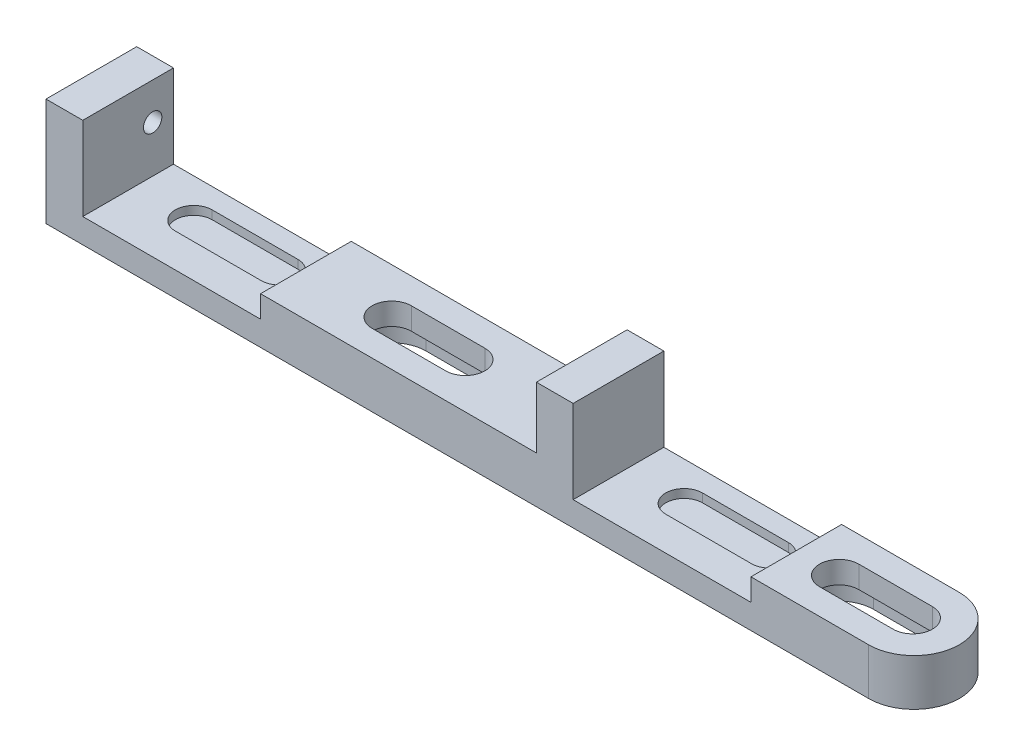
SolidWorks part; units mm, degrees
material "6061 Alloy"
ref_plane "Front Plane" through (0, 0, 0) normal (0, 0, 1) x (1, 0, 0)
ref_plane "Top Plane" through (0, 0, 0) normal (0, 1, 0) x (1, 0, 0)
ref_plane "Right Plane" through (0, 0, 0) normal (1, 0, 0) x (0, 0, -1)
sketch "Sketch1" plane through (0, 0, 0) normal (0, 0, 1) x (1, 0, 0)
  line L0 (0, 0) -> (0, 8.8)
  line L1 (0, 0) -> (70.8, 0)
  line L8 (70.8, 0) -> (70.8, 3.8)
  line L10 (0, 8.8) -> (3, 8.8)
  line L11 (3, 8.8) -> (3, 2)
  line L20 (40, 3.8) -> (40, 8.8)
  line L21 (40, 8.8) -> (43, 8.8)
  line L22 (43, 8.8) -> (43, 2)
  line L23 (40, 3.8) -> (17.5, 3.8)
  line L24 (17.5, 3.8) -> (17.5, 2)
  line L25 (17.5, 2) -> (3, 2)
  line L26 (70.8, 3.8) -> (57.5, 3.8)
  line L27 (57.5, 3.8) -> (57.5, 2)
  line L28 (57.5, 2) -> (43, 2)
  dimension "D1" = 3
  dimension "D2" = 2
  dimension "D3" = 8.8
  dimension "D4" = 3.8
  dimension "D5" = 14.5
  dimension "D6" = 3
  dimension "D7" = 40
  dimension "D8" = 14.5
  dimension "D10" = 70.8
extrude "Boss-Extrude1" add sketch "Sketch1" along normal blind 7.4
sketch "Sketch3" plane through (0, 3.8, 0) normal (0, 1, 0) x (1, 0, 0)
  line L0 (30.5, -3.7) -> (24.5, -3.7) construction
  line L1 (30.5, -5.3) -> (24.5, -5.3)
  line L2 (30.5, -2.1) -> (24.5, -2.1)
  line L3 (67, -3.7) -> (61, -3.7) construction
  line L4 (67, -5.3) -> (61, -5.3)
  line L5 (67, -2.1) -> (61, -2.1)
  line L6 (40, -7.4) -> (40, 0) construction
  arc A0 (30.5, -5.3) -> (30.5, -2.1) centre (30.5, -3.7) ccw
  arc A1 (24.5, -2.1) -> (24.5, -5.3) centre (24.5, -3.7) ccw
  arc A2 (67, -5.3) -> (67, -2.1) centre (67, -3.7) ccw
  arc A3 (61, -2.1) -> (61, -5.3) centre (61, -3.7) ccw
  point P2 (27.5, -3.7)
  point P7 (64, -3.7)
  point P21 (40, -3.7)
  dimension "D2" = 1.6
  dimension "D1" = 6
  dimension "D3" = 12.5
  dimension "D4" = 36.5
extrude "Cut-Extrude1" cut sketch "Sketch3" against normal blind 10
sketch "Sketch4" plane through (0, 0, 0) normal (0, -1, 0) x (1, 0, 0)
  line L0 (24.5, 5.3) -> (30.5, 5.3) construction
  line L1 (30.5, 2.1) -> (24.5, 2.1) construction
  line L2 (24.5, 5.3) -> (30.5, 5.3)
  line L3 (30.5, 2.1) -> (24.5, 2.1)
  line L4 (61, 5.3) -> (67, 5.3) construction
  line L5 (67, 2.1) -> (61, 2.1) construction
  line L6 (61, 5.3) -> (67, 5.3)
  line L7 (67, 2.1) -> (61, 2.1)
  line L8 (24.5, 6.5) -> (30.5, 6.5)
  line L9 (30.5, 0.9) -> (24.5, 0.9)
  line L10 (61, 6.5) -> (67, 6.5)
  line L11 (67, 0.9) -> (61, 0.9)
  arc A0 (30.5, 2.1) -> (30.5, 5.3) centre (30.5, 3.7) ccw construction
  arc A1 (24.5, 5.3) -> (24.5, 2.1) centre (24.5, 3.7) ccw construction
  arc A2 (30.5, 2.1) -> (30.5, 5.3) centre (30.5, 3.7) ccw
  arc A3 (24.5, 5.3) -> (24.5, 2.1) centre (24.5, 3.7) ccw
  arc A4 (61, 5.3) -> (61, 2.1) centre (61, 3.7) ccw construction
  arc A5 (67, 2.1) -> (67, 5.3) centre (67, 3.7) ccw construction
  arc A6 (61, 5.3) -> (61, 2.1) centre (61, 3.7) ccw
  arc A7 (67, 2.1) -> (67, 5.3) centre (67, 3.7) ccw
  arc A8 (30.5, 0.9) -> (30.5, 6.5) centre (30.5, 3.7) ccw
  arc A9 (24.5, 6.5) -> (24.5, 0.9) centre (24.5, 3.7) ccw
  arc A10 (67, 0.9) -> (67, 6.5) centre (67, 3.7) ccw
  arc A11 (61, 6.5) -> (61, 0.9) centre (61, 3.7) ccw
  dimension "D1" = 1.2
  dimension "D2" = 1.2
extrude "Cut-Extrude2" cut sketch "Sketch4" against normal blind 2
sketch "Sketch5" plane through (0, 0, 0) normal (-1, 0, 0) x (0, 0, 1)
  line L0 (7.4, 8.8) -> (0, 8.8) construction
  line L2 (7.4, 8.8) -> (7.4, 0) construction
  circle A0 centre (1.7, 5.8) radius 0.75
  dimension "D1" = 1.5
  dimension "D2" = 3
  dimension "D3" = 5.7
extrude "Cut-Extrude3" cut sketch "Sketch5" against normal up to next
sketch "Sketch6" plane through (0, 0, 0) normal (0, -1, 0) x (1, 0, 0)
  line L0 (70.8, 0) -> (70.8, 7.4)
  line L1 (70.8, 7.4) -> (70.8, 0) construction
  line L2 (70.8, 7.4) -> (67.1, 7.4)
  line L3 (0, 7.4) -> (70.8, 7.4) construction
  line L4 (0, 0) -> (70.8, 0) construction
  line L5 (67.1, 0) -> (70.8, 0)
  arc A0 (67.1, 7.4) -> (67.1, 0) centre (67.1, 3.7) cw
extrude "Cut-Extrude4" cut sketch "Sketch6" against normal blind 10 contours A0 | A0 L0 region at (69.9735, 0, 0.8265) region at (69.9735, 0, 6.5735)
sketch "Sketch7" plane through (0, 2, 0) normal (0, 1, 0) x (1, 0, 0)
  line L0 (54.8, -3.15) -> (47.8, -3.15) construction
  line L1 (54.8, -4.65) -> (47.8, -4.65)
  line L2 (54.8, -1.65) -> (47.8, -1.65)
  line L3 (14.8, -3.15) -> (7.8, -3.15) construction
  line L4 (14.8, -4.65) -> (7.8, -4.65)
  line L5 (14.8, -1.65) -> (7.8, -1.65)
  line L6 (57.5, 0) -> (43, 0) construction
  line L7 (57.5, -7.4) -> (57.5, 0) construction
  line L8 (17.5, -7.4) -> (17.5, 0) construction
  arc A0 (54.8, -4.65) -> (54.8, -1.65) centre (54.8, -3.15) ccw
  arc A1 (47.8, -1.65) -> (47.8, -4.65) centre (47.8, -3.15) ccw
  arc A2 (14.8, -4.65) -> (14.8, -1.65) centre (14.8, -3.15) ccw
  arc A3 (7.8, -1.65) -> (7.8, -4.65) centre (7.8, -3.15) ccw
  point P2 (51.3, -3.15)
  point P7 (11.3, -3.15)
  point P16 (50.25, 0)
  dimension "D2" = 1.5
  dimension "D4" = 2.7
  dimension "D5" = 2.7
  dimension "D1" = 3.15
  dimension "D3" = 7
extrude "Cut-Extrude5" cut sketch "Sketch7" against normal blind 0.7
sketch "Sketch8" [suppressed] plane through (0, 2, 0) normal (0, 1, 0) x (1, 0, 0)
  line L0 (7.8, -4.25) -> (14.8, -4.25) construction
  line L1 (7.8, -2.75) -> (14.8, -2.75)
  line L2 (7.8, -5.75) -> (14.8, -5.75)
  line L3 (47.8, -4.25) -> (54.8, -4.25) construction
  line L4 (47.8, -2.75) -> (54.8, -2.75)
  line L5 (47.8, -5.75) -> (54.8, -5.75)
  line L6 (17.5, -7.4) -> (17.5, 0) construction
  line L7 (17.5, -7.4) -> (3, -7.4) construction
  line L8 (57.5, -7.4) -> (57.5, 0) construction
  arc A0 (7.8, -2.75) -> (7.8, -5.75) centre (7.8, -4.25) ccw
  arc A1 (14.8, -5.75) -> (14.8, -2.75) centre (14.8, -4.25) ccw
  arc A2 (47.8, -2.75) -> (47.8, -5.75) centre (47.8, -4.25) ccw
  arc A3 (54.8, -5.75) -> (54.8, -2.75) centre (54.8, -4.25) ccw
  point P2 (11.3, -4.25)
  point P7 (51.3, -4.25)
  dimension "D2" = 2.7
  dimension "D3" = 1.5
  dimension "D5" = 2.7
  dimension "D1" = 7
  dimension "D4" = 3.15
extrude "Cut-Extrude6" [suppressed] cut sketch "Sketch8" against normal blind 0.7
